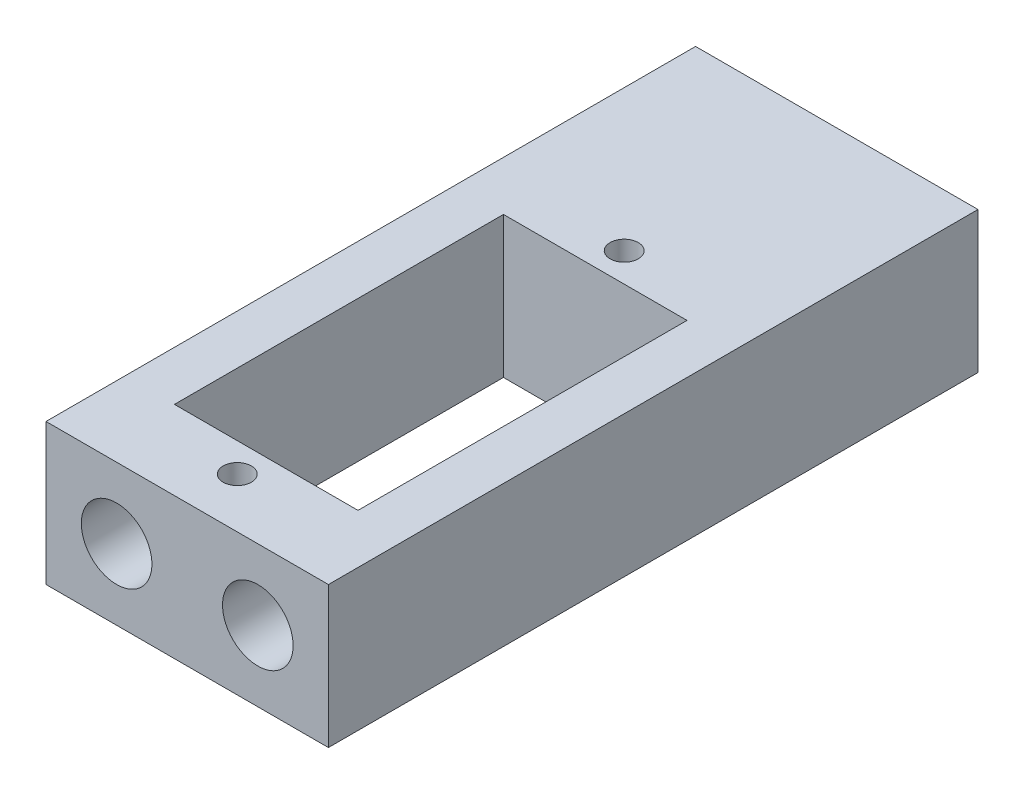
SolidWorks part; units mm, degrees
ref_plane "Front Plane" through (0, 0, 0) normal (0, 0, 1) x (1, 0, 0)
ref_plane "Top Plane" through (0, 0, 0) normal (0, 1, 0) x (1, 0, 0)
ref_plane "Right Plane" through (0, 0, 0) normal (1, 0, 0) x (0, 0, -1)
sketch "Sketch1" plane through (0, 0, 0) normal (0, 1, 0) x (1, 0, 0)
  line L1 (-10, 23) -> (10, 23)
  line L2 (-10, 23) -> (-10, -23)
  line L3 (-10, -23) -> (10, -23)
  line L4 (10, 23) -> (10, -23)
  line L5 (-10, 23) -> (10, -23) construction
  line L6 (-10, -23) -> (10, 23) construction
  point P0 (0, 0)
  dimension "D1" = 20
  dimension "D2" = 46
extrude "Boss-Extrude1" add sketch "Sketch1" along normal blind 10
sketch "Sketch2" plane through (0, 10, 0) normal (0, 1, 0) x (1, 0, 0)
  line L0 (6.5, -5.755) -> (-6.5, -5.755) construction
  line L1 (-6.5, 5.895) -> (6.5, 5.895)
  line L2 (-6.5, 5.895) -> (-6.5, -17.405)
  line L3 (-6.5, -17.405) -> (6.5, -17.405)
  line L4 (6.5, 5.895) -> (6.5, -17.405)
  line L5 (-6.5, 5.895) -> (6.5, -17.405) construction
  line L6 (-6.5, -17.405) -> (6.5, 5.895) construction
  line L7 (10, 0) -> (-10, 0) construction
  line L8 (10, -23) -> (10, 23) construction
  line L9 (-10, 23) -> (-10, -23) construction
  line L10 (0, 23) -> (0, -23) construction
  line L11 (10, 23) -> (-10, 23) construction
  line L12 (-10, -23) -> (10, -23) construction
  circle A0 centre (0, 7.945) radius 1
  circle A1 centre (0, -19.455) radius 1
  point P0 (0, -5.755)
  dimension "D4" = 2
  dimension "D1" = 17.405
  dimension "D2" = 13
  dimension "D3" = 23.3
  dimension "D5" = 27.4
extrude "Cut-Extrude1" cut sketch "Sketch2" against normal through all
sketch "Sketch3" plane through (0, 0, -23) normal (0, 0, -1) x (-1, 0, 0)
  line L0 (10, 5) -> (-10, 5) construction
  line L1 (10, 10) -> (10, 0) construction
  line L2 (-10, 10) -> (-10, 0) construction
  line L3 (0, 0) -> (0, 10) construction
  line L4 (-10, 0) -> (10, 0) construction
  line L5 (-10, 10) -> (10, 10) construction
  circle A0 centre (5, 5) radius 2.5
  circle A1 centre (-5, 5) radius 2.5
  dimension "D1" = 5
  dimension "D2" = 10
extrude "Cut-Extrude2" cut sketch "Sketch3" against normal blind 4
sketch "Sketch4" plane through (0, 0, 23) normal (0, 0, 1) x (1, 0, 0)
  line L0 (20, 5) -> (-20, 5) construction
  line L3 (0, 0) -> (0, 10) construction
  circle A0 centre (5, 5) radius 2.5
  circle A1 centre (-5, 5) radius 2.5
  dimension "D1" = 5
  dimension "D2" = 10
extrude "Cut-Extrude3" cut sketch "Sketch4" against normal blind 4
